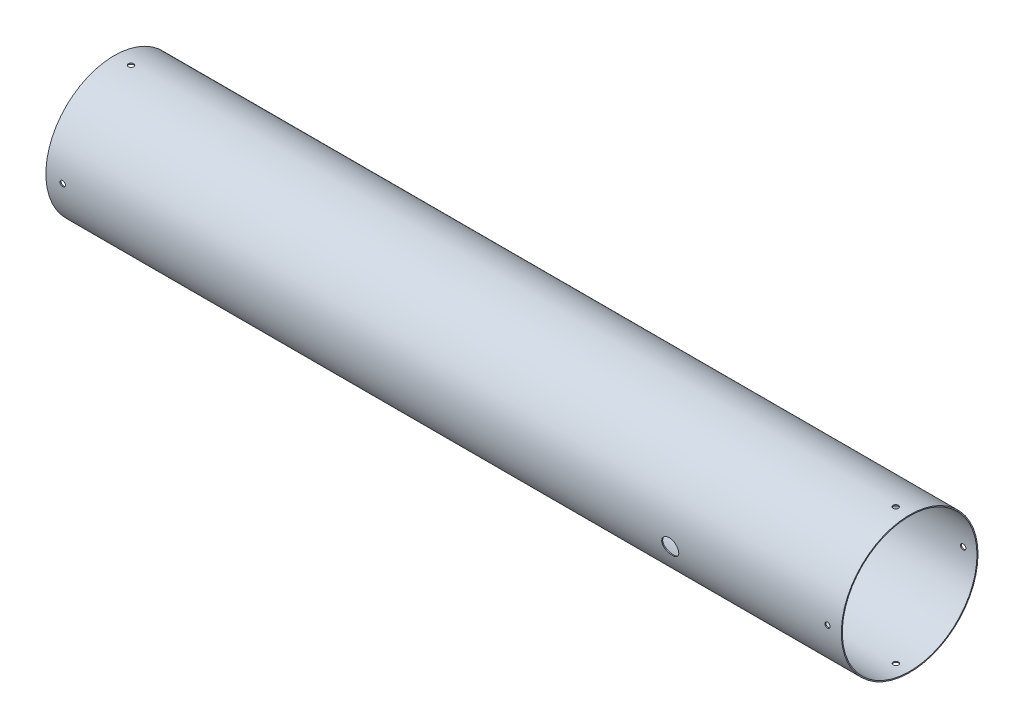
SolidWorks part; units mm, degrees
ref_plane "Front Plane" through (0, 0, 0) normal (0, 0, 1) x (1, 0, 0)
ref_plane "Top Plane" through (0, 0, 0) normal (0, 1, 0) x (1, 0, 0)
ref_plane "Right Plane" through (0, 0, 0) normal (1, 0, 0) x (0, 0, -1)
sketch "Sketch1" plane through (0, 0, 0) normal (1, 0, 0) x (0, 0, -1)
  circle A0 centre (0, 0) radius 51.562
  circle A1 centre (0, 0) radius 50.8
  dimension "D1" = 103.124
  dimension "D2" = 101.6
extrude "Boss-Extrude1" add sketch "Sketch1" along normal mid plane 600
sketch "Sketch3" plane through (0, 0, 0) normal (0, 0, 1) x (1, 0, 0)
  line L0 (300, -51.562) -> (300, 51.562) construction
  circle A1 centre (170.18, -8.89) radius 6.35
  dimension "D2" = 12.7
  dimension "D3" = 8.89
  dimension "D1" = 129.82
extrude "Cut-Extrude1" cut sketch "Sketch3" against normal through all both and the other way through all
sketch "Sketch4" plane through (0, 0, 0) normal (0, 0, 1) x (1, 0, 0)
  line L0 (300, -51.562) -> (300, 51.562) construction
  line L1 (-300, 51.562) -> (-300, -51.562) construction
  circle A0 centre (289.586, 0) radius 2
  circle A1 centre (-287.3, 0) radius 2
  dimension "D2" = 4
  dimension "D3" = 4
  dimension "D1" = 10.414
  dimension "D4" = 12.7
extrude "Cut-Extrude2" cut sketch "Sketch4" against normal through all both and the other way through all contours A1 | A0 region at (-287.3, 0, 0)
pattern_circular "CirPattern1" count 2 every 90 about axis through (300, 0, 0) along (-1, 0, 0) of "Cut-Extrude2"
